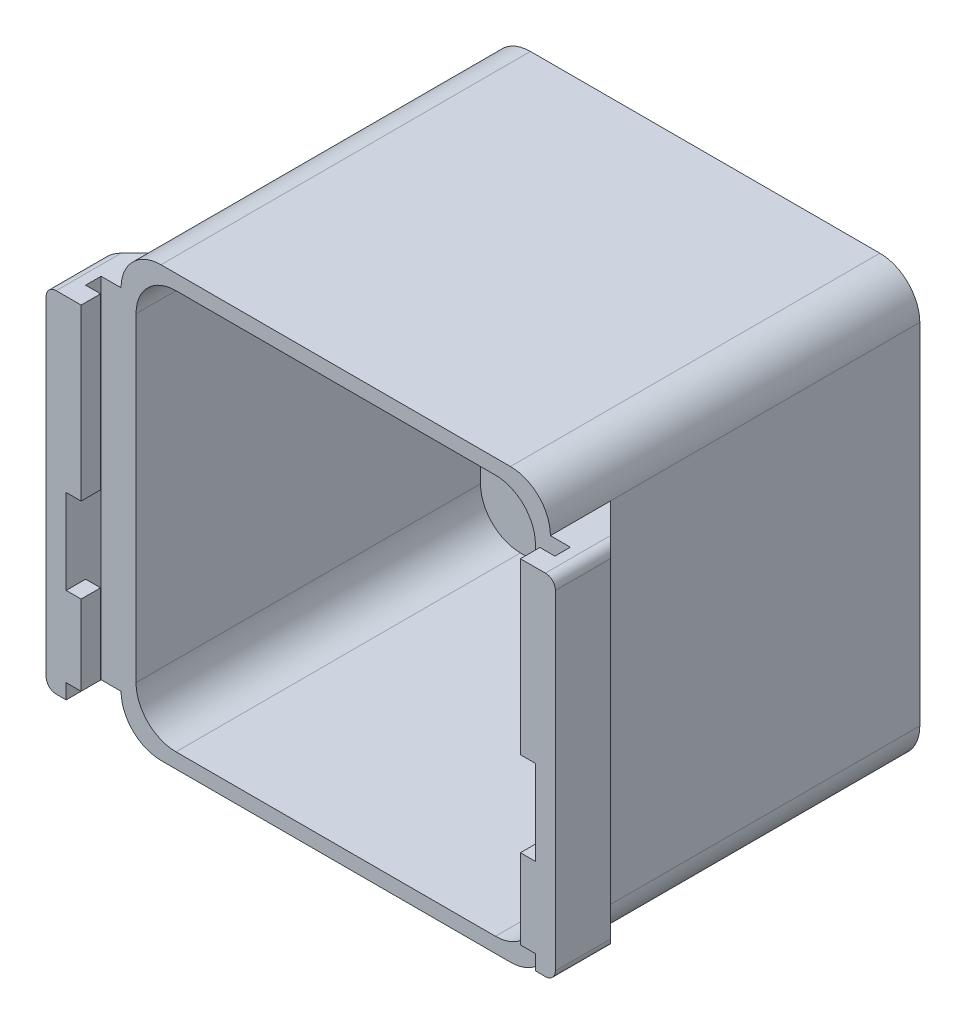
SolidWorks part; units mm, degrees
ref_plane "前视基准面" through (0, 0, 0) normal (0, 0, 1) x (1, 0, 0)
ref_plane "上视基准面" through (0, 0, 0) normal (0, 1, 0) x (1, 0, 0)
ref_plane "右视基准面" through (0, 0, 0) normal (1, 0, 0) x (0, 0, -1)
sketch "草图1" plane through (0, 0, 0) normal (0, 0, 1) x (1, 0, 0)
  line L1 (-40, 40) -> (40, 40)
  line L2 (-40, 40) -> (-40, -40)
  line L3 (-40, -40) -> (40, -40)
  line L4 (40, 40) -> (40, -40)
  line L5 (-40, 40) -> (40, -40) construction
  line L6 (-40, -40) -> (40, 40) construction
  point P0 (0, 0)
  dimension "D1" = 80
extrude "凸台-拉伸1" add sketch "草图1" along normal blind 70
shell "抽壳1" thickness 3 removed face at (0, 0, 70) outward yes
sketch "草图2" plane through (0, 0, 0) normal (0, 0, 1) x (1, 0, 0)
  line L1 (-21, 21) -> (21, 21)
  line L2 (-21, 21) -> (-21, -21)
  line L3 (-21, -21) -> (21, -21)
  line L4 (21, 21) -> (21, -21)
  line L5 (-21, 21) -> (21, -21) construction
  line L6 (-21, -21) -> (21, 21) construction
  line L10 (40, -40) -> (40, 40)
  line L11 (40, 40) -> (-40, 40)
  line L12 (-40, 40) -> (-40, -40)
  line L13 (-40, -40) -> (40, -40)
  line L14 (40, -40) -> (40, 40)
  line L15 (40, 40) -> (-40, 40)
  line L16 (-40, 40) -> (-40, -40)
  line L17 (-40, -40) -> (40, -40)
  point P0 (0, 0)
  dimension "D1" = 42
  dimension "D2" = 0
extrude "凸台-拉伸2" add sketch "草图2" along normal blind 1
fillet "圆角1" radius 8 8 edges at (43, -43, 33.5) (40, -40, 35.5) (-40, -40, 35.5) (-43, -43, 33.5) (43, 43, 33.5) (-43, 43, 33.5) (40, 40, 35.5) (-40, 40, 35.5)
sketch "草图3" plane through (-43, 0, 0) normal (-1, 0, 0) x (0, 0, 1)
  line L0 (70, 35) -> (-3, 35) construction
  line L1 (66, 35) -> (70, 35)
  line L2 (66, 35) -> (66, -35)
  line L3 (66, -35) -> (70, -35)
  line L4 (70, 35) -> (70, -35)
  dimension "D1" = 4
extrude "凸台-拉伸3" add sketch "草图3" along normal blind 8
sketch "草图4" plane through (0, 0, 70) normal (0, 0, 1) x (1, 0, 0)
  line L0 (-51, -35) -> (-43, -35) construction
  line L1 (-51, 35) -> (-47, 35)
  line L2 (-51, 35) -> (-51, -35)
  line L3 (-51, -35) -> (-47, -35)
  line L4 (-47, 35) -> (-47, -35)
  line L5 (-43, 35) -> (-43, -35) construction
  dimension "D1" = 4
extrude "凸台-拉伸4" add sketch "草图4" along normal blind 7
sketch "草图5" plane through (-47, 0, 0) normal (1, 0, 0) x (0, 0, -1)
  line L0 (-77, -35) -> (-70, -35) construction
  line L1 (-77, 35) -> (-73.1, 35)
  line L2 (-77, 35) -> (-77, -32)
  line L3 (-77, -32) -> (-73.1, -32)
  line L4 (-73.1, 35) -> (-73.1, -32)
  line L5 (-70, -35) -> (-70, 35) construction
  point P7 (-73.5, -35)
  dimension "D1" = 3
  dimension "D2" = 3.1
extrude "凸台-拉伸5" add sketch "草图5" along normal blind 3
sketch "草图8" plane through (-44, 0, 0) normal (1, 0, 0) x (0, 0, -1)
  line L0 (-73.1, -32) -> (-73.1, 35) construction
  line L1 (-77, 35) -> (-77, -32) construction
  line L2 (-77, 1) -> (-73.1, 1)
  line L3 (-77, 1) -> (-77, -16)
  line L4 (-77, -16) -> (-73.1, -16)
  line L5 (-73.1, 1) -> (-73.1, -16)
  line L6 (-77, -32) -> (-73.1, -32) construction
  dimension "D1" = 16
  dimension "D2" = 17
extrude "切除-拉伸2" cut sketch "草图8" against normal up to surface (3 mm away) up to face at (-47, -10.6667, 73.3667)
mirror "镜向1" about plane through (0, 0, 0) normal (1, 0, 0) of "切除-拉伸2", "凸台-拉伸4", "凸台-拉伸5", "凸台-拉伸3"
fillet "圆角2" radius 2 4 edges at (51, 35, 71.5) (51, -35, 71.5) (-51, -35, 71.5) (-51, 35, 71.5)
chamfer "倒角1" distance 8 angle 45 2 edges at (43, 0, 66) (-43, 0, 66)
sketch "草图6" plane through (0, 0, -3) normal (0, 0, -1) x (-1, 0, 0)
  line L4 (-43, 35) -> (-43, -35)
  line L5 (-35, -43) -> (35, -43)
  line L6 (43, -35) -> (43, 35)
  line L7 (35, 43) -> (-35, 43)
  line L8 (-43, 35) -> (-43, -35)
  line L9 (-35, -43) -> (35, -43)
  line L10 (43, -35) -> (43, 35)
  line L11 (35, 43) -> (-35, 43)
  arc A4 (-43, -35) -> (-35, -43) centre (-35, -35) ccw
  arc A5 (35, -43) -> (43, -35) centre (35, -35) ccw
  arc A6 (43, 35) -> (35, 43) centre (35, 35) ccw
  arc A7 (-35, 43) -> (-43, 35) centre (-35, 35) ccw
  arc A8 (-43, -35) -> (-35, -43) centre (-35, -35) ccw
  arc A9 (35, -43) -> (43, -35) centre (35, -35) ccw
  arc A10 (43, 35) -> (35, 43) centre (35, 35) ccw
  arc A11 (-35, 43) -> (-43, 35) centre (-35, 35) ccw
  dimension "D1" = 0
extrude "凸台-拉伸6" add sketch "草图6" along normal blind 1
sketch "草图7" plane through (0, 0, -4) normal (0, 0, -1) x (-1, 0, 0)
  circle A0 centre (0, 0) radius 5.5
  dimension "D1" = 11
extrude "切除-拉伸1" cut sketch "草图7" against normal blind 2
pattern_linear "阵列(线性)1" count 3 spacing 14 along (-1, 0, 0) count 3 spacing 14 along (0, -1, 0) of "切除-拉伸1"
mirror "镜向2" about plane through (0, 0, 0) normal (0, 1, 0) of "阵列(线性)1"
mirror "镜向3" about plane through (0, 0, 0) normal (1, 0, 0) of "阵列(线性)1", "镜向2"
